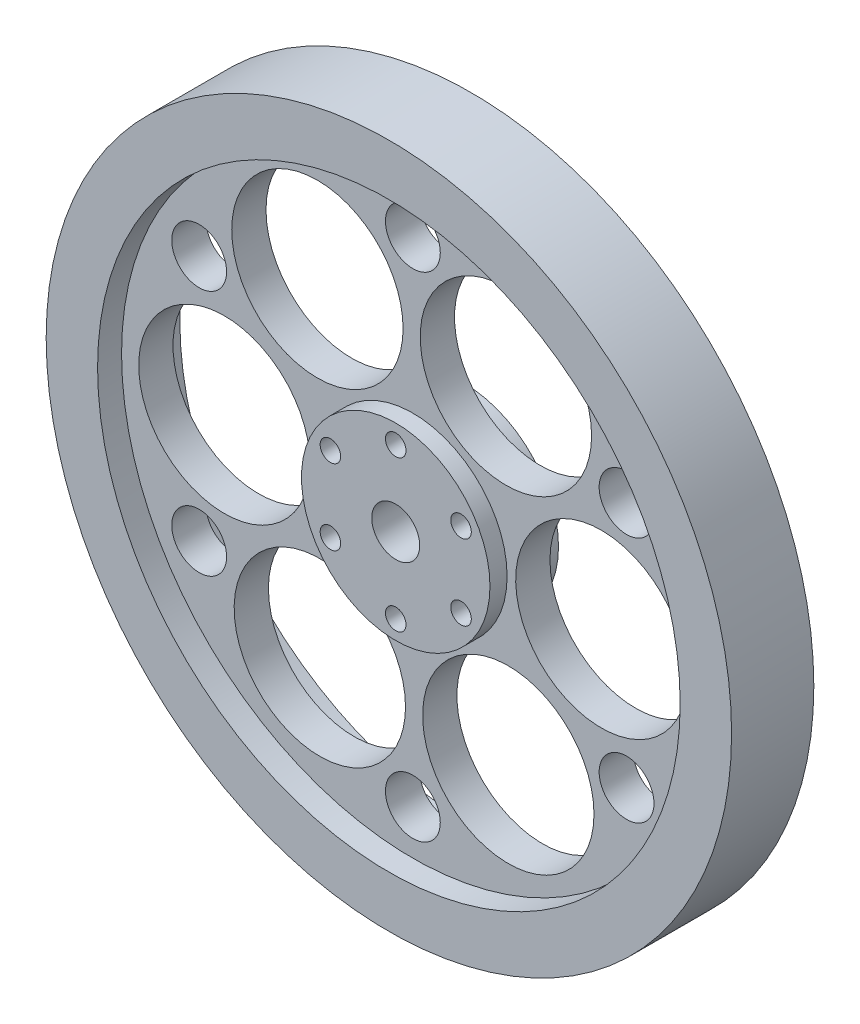
SolidWorks part; units mm, degrees
ref_plane "Front Plane" through (0, 0, 0) normal (0, 0, 1) x (1, 0, 0)
ref_plane "Top Plane" through (0, 0, 0) normal (0, 1, 0) x (1, 0, 0)
ref_plane "Right Plane" through (0, 0, 0) normal (1, 0, 0) x (0, 0, -1)
sketch "Sketch1" plane through (0, 0, 0) normal (0, 0, 1) x (1, 0, 0)
  circle A0 centre (0, 0) radius 85
  circle A1 centre (0, 0) radius 100
  circle A2 centre (0, 0) radius 27.5
  dimension "D1" = 200
  dimension "D2" = 170
  dimension "D3" = 55
extrude "Boss-Extrude1" add sketch "Sketch1" along normal blind 10 and the other way blind 10 contours A2 region at (0, 0, 0)
extrude "Boss-Extrude2" add sketch "Sketch1<3>" along normal blind 12 and the other way blind 12 separate body contours A1 A0 region at (-97.1716, 0, 0)
sketch "Sketch1<3>" plane through (0, 0, 0) normal (0, 0, 1) x (1, 0, 0) same geometry as "Sketch1"
extrude "Boss-Extrude3" add sketch "Sketch1<4>" along normal blind 5 and the other way blind 5 contours A0 A2 region at (-82.5958, 0, 0)
sketch "Sketch1<4>" plane through (0, 0, 0) normal (0, 0, 1) x (1, 0, 0) same geometry as "Sketch1"
sketch "Sketch2" plane through (0, 0, 10) normal (0, 0, 1) x (1, 0, 0)
  circle A0 centre (0, 0) radius 7
  dimension "D1" = 14
extrude "Cut-Extrude1" cut sketch "Sketch2" against normal through all
sketch "Sketch3" plane through (0, 0, 10) normal (0, 0, 1) x (1, 0, 0)
  line L0 (0, 9.8708) -> (0, -10.2985) construction
  line L1 (0, -10.2985) -> (0, 0) construction
  line L2 (0, 0) -> (12.3296, 0) construction
  line L3 (12.3296, 0) -> (-10.4054, 0) construction
  line L4 (-10.4054, 0) -> (0, 0) construction
  line L5 (0, 0) -> (12.2741, 7.0864) construction
  line L6 (12.2741, 7.0864) -> (-10.1002, -5.8314) construction
  line L8 (-10.7309, 6.332) -> (11.7585, -6.6522) construction
  circle A0 centre (0, 0) radius 22
  circle A1 centre (0, 0) radius 72
  circle A2 centre (0, 22) radius 3
  circle A3 centre (0, 72) radius 8
  circle A5 centre (62.3538, 36) radius 8
  circle A6 centre (19.0526, 11) radius 3
  circle A7 centre (62.3538, -36) radius 8
  circle A8 centre (19.0526, -11) radius 3
  circle A9 centre (0, -72) radius 8
  circle A10 centre (0, -22) radius 3
  circle A11 centre (-62.3538, -36) radius 8
  circle A12 centre (-19.0526, -11) radius 3
  circle A13 centre (-62.3538, 36) radius 8
  circle A14 centre (-19.0526, 11) radius 3
  point P39 (0, 0)
  dimension "D4" = 6
  dimension "D6" = 16
  dimension "D7" = 144
  dimension "D9" = 44
  dimension "D1" = 60
  dimension "D2" = 60
  dimension "D3" = 60
  dimension "D5" = 60
  dimension "D8" = 6
extrude "Cut-Extrude2" cut sketch "Sketch3" against normal through all contours A1 A13 | A1 A13 | A1 A3 | A1 A3 | A1 A5 | A1 A5 | A1 A7 | A1 A7 | A1 A9 | A1 A9 | A1 A11 | A1 A11 | A14 | A2 | A6 | A8 | A10 | A12 region at (59.3452, 34.263, 10) region at (65.2238, 37.657, 10) region at (65.2238, -37.657, 10) region at (59.3452, -34.263, 10) region at (0, 68.5259, 10) region at (0, 75.314, 10) region at (0, -75.314, 10) region at (0, -68.5259, 10) region at (-59.3452, 34.263, 10) region at (-65.2238, 37.657, 10) region at (-65.2238, -37.657, 10) region at (-59.3452, -34.263, 10)
sketch "Sketch4" plane through (0, 0, -5) normal (0, 0, -1) x (-1, 0, 0)
  circle A0 centre (0, 0) radius 55
  circle A1 centre (27.8517, 47.4266) radius 25
  dimension "D1" = 110
  dimension "D2" = 50
extrude "Cut-Extrude3" cut sketch "Sketch4" against normal through all contours A0 A1 | A0 A1 region at (-21.9948, 37.4534, -5) region at (-32.6731, 55.6367, -5)
pattern_circular "CirPattern1" count 6 over 360 about axis through (0, 0, -10) along (0, 0, 1) of "Cut-Extrude3"
